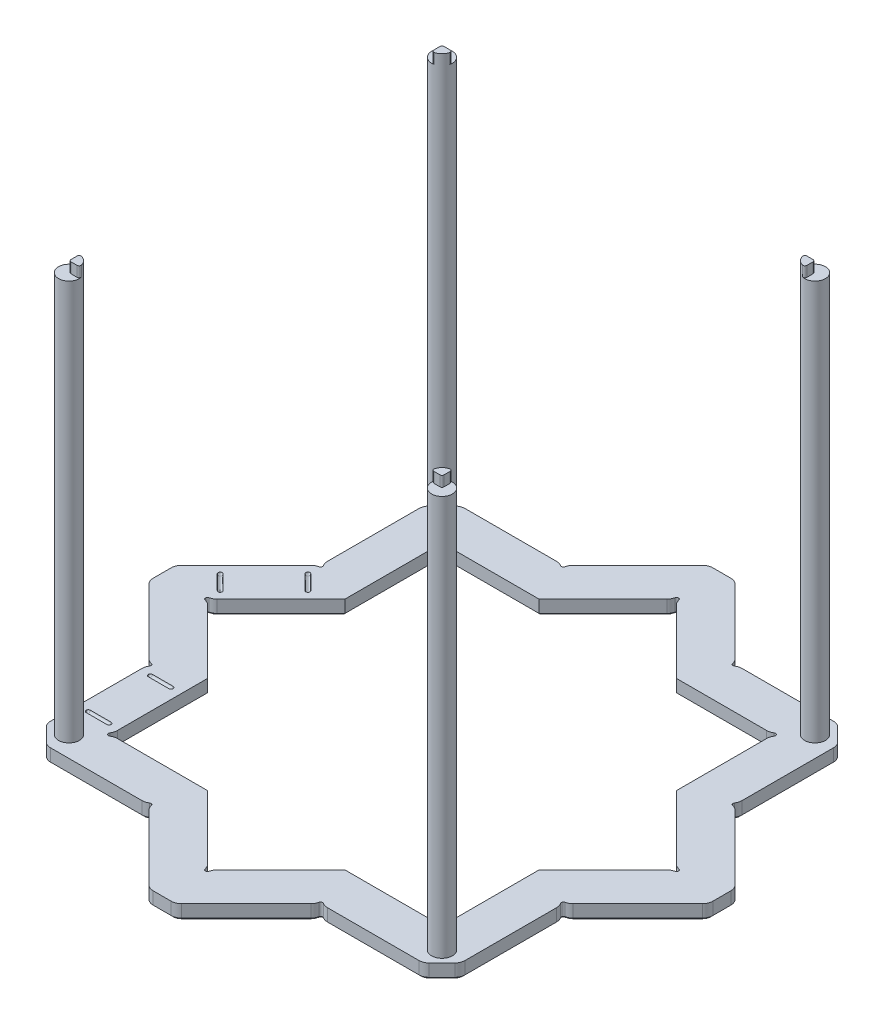
SolidWorks part; units mm, degrees
ref_plane "前视基准面" through (0, 0, 0) normal (0, 0, 1) x (1, 0, 0)
ref_plane "上视基准面" through (0, 0, 0) normal (0, 1, 0) x (1, 0, 0)
ref_plane "右视基准面" through (0, 0, 0) normal (1, 0, 0) x (0, 0, -1)
sketch "草图1" plane through (0, 0, 0) normal (0, 1, 0) x (1, 0, 0)
  line L0 (70.7107, 0) -> (0, 70.7107)
  line L1 (-50, 50) -> (50, 50)
  line L2 (-50, 50) -> (-50, -50)
  line L3 (-50, -50) -> (50, -50)
  line L4 (50, 50) -> (50, -50)
  line L5 (-50, 50) -> (50, -50) construction
  line L6 (-50, -50) -> (50, 50) construction
  line L7 (70.7107, 0) -> (0, -70.7107)
  line L8 (0, 70.7107) -> (-70.7107, 0)
  line L9 (0, -70.7107) -> (-70.7107, 0)
  line L10 (70.7107, 0) -> (-70.7107, 0) construction
  line L11 (0, 70.7107) -> (0, -70.7107) construction
  point P0 (0, 0)
  point P7 (0, 0)
  dimension "D1" = 100
  dimension "D2" = 100
  dimension "D3" = 100
  dimension "D4" = 100
extrude "凸台-拉伸1" add sketch "草图1" along normal blind 3.5 contours L0 L8 L1 | L4 L1 L0 | L7 L0 L4 | L9 L7 L3 | L4 L7 L3 | L3 L9 L2 | L9 L2 L8 | L8 L1 L2 | L9 L3 L7 L4 L0 L1 L8 L2
sketch "草图2" plane through (0, 3.5, 0) normal (0, 1, 0) x (1, 0, 0)
  line L0 (-50, -50) -> (50, 50) construction
  line L1 (-2.2703, -97.7297) -> (97.7297, 2.2703)
  line L2 (-97.7297, -2.2703) -> (2.2703, 97.7297)
  line L3 (-50, 50) -> (50, -50) construction
  line L4 (67.5, 70.7107) -> (67.5, -70.7107)
  line L5 (97.7297, 2.2703) -> (-2.2703, -97.7297)
  line L6 (70.7107, -67.5) -> (-70.7107, -67.5)
  line L7 (2.2703, -97.7297) -> (-97.7297, 2.2703)
  line L12 (-97.7297, 2.2703) -> (2.2703, -97.7297)
  line L13 (-2.2703, 97.7297) -> (97.7297, -2.2703)
  line L14 (-67.5, -70.7107) -> (-67.5, 70.7107)
  line L15 (-97.7297, -2.2703) -> (2.2703, 97.7297)
  line L16 (-70.7107, 67.5) -> (70.7107, 67.5)
  line L30 (20.7107, 50) -> (0, 70.7107)
  line L31 (0, 70.7107) -> (-20.7107, 50)
  line L32 (-20.7107, 50) -> (-50, 50)
  line L33 (-50, 50) -> (-50, 20.7107)
  line L34 (-50, 20.7107) -> (-70.7107, 0)
  line L35 (-70.7107, 0) -> (-50, -20.7107)
  line L36 (-50, -20.7107) -> (-50, -50)
  line L37 (-50, -50) -> (-20.7107, -50)
  line L38 (-20.7107, -50) -> (0, -70.7107)
  line L39 (0, -70.7107) -> (20.7107, -50)
  line L40 (20.7107, -50) -> (50, -50)
  line L41 (50, -50) -> (50, -20.7107)
  line L42 (50, -20.7107) -> (70.7107, 0)
  line L43 (70.7107, 0) -> (50, 20.7107)
  line L44 (50, 20.7107) -> (50, 50)
  line L45 (50, 50) -> (20.7107, 50)
  line L46 (20.7107, 50) -> (0, 70.7107)
  line L47 (0, 70.7107) -> (-20.7107, 50)
  line L48 (-20.7107, 50) -> (-50, 50)
  line L49 (-50, 50) -> (-50, 20.7107)
  line L50 (-50, 20.7107) -> (-70.7107, 0)
  line L51 (-70.7107, 0) -> (-50, -20.7107)
  line L52 (-50, -20.7107) -> (-50, -50)
  line L53 (-50, -50) -> (-20.7107, -50)
  line L54 (-20.7107, -50) -> (0, -70.7107)
  line L55 (0, -70.7107) -> (20.7107, -50)
  line L56 (20.7107, -50) -> (50, -50)
  line L57 (50, -50) -> (50, -20.7107)
  line L58 (50, -20.7107) -> (70.7107, 0)
  line L59 (70.7107, 0) -> (50, 20.7107)
  line L60 (50, 20.7107) -> (50, 50)
  line L61 (50, 50) -> (20.7107, 50)
  line L62 (20.7107, 50) -> (0, 70.7107)
  line L63 (50, 50) -> (20.7107, 50)
  line L64 (50, 20.7107) -> (50, 50)
  line L65 (70.7107, 0) -> (50, 20.7107)
  line L66 (50, -20.7107) -> (70.7107, 0)
  line L67 (50, -50) -> (50, -20.7107)
  line L68 (20.7107, -50) -> (50, -50)
  line L69 (0, -70.7107) -> (20.7107, -50)
  line L70 (-20.7107, -50) -> (0, -70.7107)
  line L71 (-50, -50) -> (-20.7107, -50)
  line L72 (-50, -20.7107) -> (-50, -50)
  line L73 (-70.7107, 0) -> (-50, -20.7107)
  line L74 (-50, 20.7107) -> (-70.7107, 0)
  line L75 (-50, 50) -> (-50, 20.7107)
  line L76 (-20.7107, 50) -> (-50, 50)
  line L77 (0, 70.7107) -> (-20.7107, 50)
  line L78 (20.7107, 50) -> (0, 70.7107)
  line L79 (50, 50) -> (20.7107, 50)
  line L80 (50, 20.7107) -> (50, 50)
  line L81 (70.7107, 0) -> (50, 20.7107)
  line L82 (50, -20.7107) -> (70.7107, 0)
  line L83 (50, -50) -> (50, -20.7107)
  line L84 (20.7107, -50) -> (50, -50)
  line L85 (0, -70.7107) -> (20.7107, -50)
  line L86 (-20.7107, -50) -> (0, -70.7107)
  line L87 (-50, -50) -> (-20.7107, -50)
  line L88 (-50, -20.7107) -> (-50, -50)
  line L89 (-70.7107, 0) -> (-50, -20.7107)
  line L90 (-50, 20.7107) -> (-70.7107, 0)
  line L91 (-50, 50) -> (-50, 20.7107)
  line L92 (-20.7107, 50) -> (-50, 50)
  line L93 (0, 70.7107) -> (-20.7107, 50)
  point P41 (0, 0)
  dimension "D1" = 8
  dimension "D2" = 67.5
  dimension "D3" = 67.5
  dimension "D4" = 67.5
  dimension "D5" = 67.5
  dimension "D6" = 0
  dimension "D7" = 0
extrude "切除-拉伸1" cut sketch "草图2" against normal blind 13.5
fillet "圆角1" radius 2.5 16 edges at (-50, 1.75, -45.4594) (-45.4594, 1.75, -50) (45.4594, 1.75, -50) (50, 1.75, -45.4594) (45.4594, 1.75, 50) (50, 1.75, 45.4594) (-50, 1.75, 45.4594) (-45.4594, 1.75, 50) (-3.2107, 1.75, 67.5) (3.2107, 1.75, 67.5) (67.5, 1.75, 3.2107) (67.5, 1.75, -3.2107) (3.2107, 1.75, -67.5) (-3.2107, 1.75, -67.5) (-67.5, 1.75, -3.2107) (-67.5, 1.75, 3.2107)
sketch "草图3" plane through (0, 3.5, 0) normal (0, 1, 0) x (1, 0, 0)
  line L0 (0, -56.5685) -> (56.5685, 0)
  line L1 (40, -40) -> (-40, -40)
  line L2 (40, -40) -> (40, 40)
  line L3 (40, 40) -> (-40, 40)
  line L4 (-40, -40) -> (-40, 40)
  line L5 (40, -40) -> (-40, 40) construction
  line L6 (40, 40) -> (-40, -40) construction
  line L7 (-40, -40) -> (40, -40)
  line L8 (-56.5685, 0) -> (0, -56.5685)
  line L9 (-40, 40) -> (-40, -40)
  line L10 (0, 56.5685) -> (-56.5685, 0)
  line L11 (40, 40) -> (-40, 40)
  line L12 (56.5685, 0) -> (0, 56.5685)
  point P0 (0, 0)
  point P23 (0, 0)
  dimension "D1" = 80
  dimension "D2" = 80
  dimension "D3" = 8
extrude "切除-拉伸2" cut sketch "草图3" against normal blind 13.5 contours L2 L12 L11 L10 L4 L8 L1 L0 | L0 L12 L2 | L12 L2 L3 | L11 L12 L10 | L10 L3 L9 | L4 L10 L8 | L8 L4 L7 | L1 L8 L0 | L1 L2 L0
sketch "草图5" plane through (0, 3.5, 0) normal (0, 1, 0) x (1, 0, 0)
  line L1 (-16.5685, -40) -> (-40, -40) construction
  line L3 (-16.5685, -40) -> (-40, -40)
  line L4 (40, -40) -> (16.5685, -40) construction
  line L5 (40, -40) -> (16.5685, -40)
  line L6 (40, 40) -> (16.5685, 40) construction
  line L7 (40, 40) -> (16.5685, 40)
  line L9 (-40, 16.5685) -> (-40, 40) construction
  line L10 (-40, 16.5685) -> (-40, 40)
  circle A0 centre (40, -40) radius 0.5
  circle A1 centre (40, 40) radius 0.5
  circle A2 centre (-40, 40) radius 0.5
  circle A3 centre (-40, -40) radius 0.5
  circle A4 centre (56.5685, 0) radius 0.5
  circle A5 centre (40, -40) radius 0.5
  circle A6 centre (0, -56.5685) radius 0.5
  circle A7 centre (-40, -40) radius 0.5
  circle A8 centre (-56.5685, 0) radius 0.5
  circle A9 centre (-40, 40) radius 0.5
  circle A10 centre (0, 56.5685) radius 0.5
  point P30 (0, 0)
  dimension "D1" = 1
  dimension "D2" = 1
  dimension "D3" = 1
  dimension "D4" = 1
  dimension "D5" = 8
extrude "切除-拉伸3" cut sketch "草图5" against normal blind 13.5
fillet "圆角2" radius 2.5 16 edges at (56.215, 1.75, 0.3536) (40, 1.75, -39.5) (0.3536, 1.75, -56.215) (-39.5, 1.75, -40) (-56.215, 1.75, -0.3536) (-40, 1.75, 39.5) (-0.3536, 1.75, 56.215) (39.5, 1.75, 40) (-39.5, 1.75, 40) (-40, 1.75, -39.5) (39.5, 1.75, -40) (56.215, 1.75, -0.3536) (0.3536, 1.75, 56.215) (-56.215, 1.75, 0.3536) (-0.3536, 1.75, -56.215) (40, 1.75, 39.5)
sketch "草图13" plane through (0, 3.5, 0) normal (0, 1, 0) x (1, 0, 0)
  line L1 (45, 45) -> (-45, 45) construction
  line L2 (45, 45) -> (45, -45) construction
  line L3 (45, -45) -> (-45, -45) construction
  line L4 (-45, 45) -> (-45, -45) construction
  line L5 (45, 45) -> (-45, -45) construction
  line L6 (45, -45) -> (-45, 45) construction
  line L46 (2.1751, 67.5) -> (-2.1751, 67.5)
  line L47 (20.7107, 50) -> (3.9429, 66.7678)
  line L48 (44.4239, 50) -> (20.7107, 50)
  line L49 (49.2678, 46.1916) -> (46.1916, 49.2678)
  line L50 (50, 20.7107) -> (50, 44.4239)
  line L51 (66.7678, 3.9429) -> (50, 20.7107)
  line L52 (67.5, -2.1751) -> (67.5, 2.1751)
  line L53 (50, -20.7107) -> (66.7678, -3.9429)
  line L54 (50, -44.4239) -> (50, -20.7107)
  line L55 (46.1916, -49.2678) -> (49.2678, -46.1916)
  line L56 (20.7107, -50) -> (44.4239, -50)
  line L57 (3.9429, -66.7678) -> (20.7107, -50)
  line L58 (-2.1751, -67.5) -> (2.1751, -67.5)
  line L59 (-20.7107, -50) -> (-3.9429, -66.7678)
  line L60 (-44.4239, -50) -> (-20.7107, -50)
  line L61 (-49.2678, -46.1916) -> (-46.1916, -49.2678)
  line L62 (-50, -20.7107) -> (-50, -44.4239)
  line L63 (-66.7678, -3.9429) -> (-50, -20.7107)
  line L64 (-67.5, 2.1751) -> (-67.5, -2.1751)
  line L65 (-50, 20.7107) -> (-66.7678, 3.9429)
  line L66 (-50, 44.4239) -> (-50, 20.7107)
  line L67 (-46.1916, 49.2678) -> (-49.2678, 46.1916)
  line L68 (-20.7107, 50) -> (-44.4239, 50)
  line L69 (-3.9429, 66.7678) -> (-20.7107, 50)
  line L70 (2.1751, 67.5) -> (-2.1751, 67.5)
  line L71 (20.7107, 50) -> (3.9429, 66.7678)
  line L72 (44.4239, 50) -> (20.7107, 50)
  line L73 (49.2678, 46.1916) -> (46.1916, 49.2678)
  line L74 (50, 20.7107) -> (50, 44.4239)
  line L75 (66.7678, 3.9429) -> (50, 20.7107)
  line L76 (67.5, -2.1751) -> (67.5, 2.1751)
  line L77 (50, -20.7107) -> (66.7678, -3.9429)
  line L78 (50, -44.4239) -> (50, -20.7107)
  line L79 (46.1916, -49.2678) -> (49.2678, -46.1916)
  line L80 (20.7107, -50) -> (44.4239, -50)
  line L81 (3.9429, -66.7678) -> (20.7107, -50)
  line L82 (-2.1751, -67.5) -> (2.1751, -67.5)
  line L83 (-20.7107, -50) -> (-3.9429, -66.7678)
  line L84 (-44.4239, -50) -> (-20.7107, -50)
  line L85 (-49.2678, -46.1916) -> (-46.1916, -49.2678)
  line L86 (-50, -20.7107) -> (-50, -44.4239)
  line L87 (-66.7678, -3.9429) -> (-50, -20.7107)
  line L88 (-67.5, 2.1751) -> (-67.5, -2.1751)
  line L89 (-50, 20.7107) -> (-66.7678, 3.9429)
  line L90 (-50, 44.4239) -> (-50, 20.7107)
  line L91 (-46.1916, 49.2678) -> (-49.2678, 46.1916)
  line L92 (-20.7107, 50) -> (-44.4239, 50)
  line L93 (-3.9429, 66.7678) -> (-20.7107, 50)
  circle A0 centre (45, 45) radius 2.5
  circle A1 centre (45, -45) radius 2.5
  circle A2 centre (-45, -45) radius 2.5
  circle A3 centre (-45, 45) radius 2.5
  arc A36 (3.9429, 66.7678) -> (2.1751, 67.5) centre (2.1751, 65) ccw
  arc A37 (46.1916, 49.2678) -> (44.4239, 50) centre (44.4239, 47.5) ccw
  arc A38 (50, 44.4239) -> (49.2678, 46.1916) centre (47.5, 44.4239) ccw
  arc A39 (67.5, 2.1751) -> (66.7678, 3.9429) centre (65, 2.1751) ccw
  arc A40 (66.7678, -3.9429) -> (67.5, -2.1751) centre (65, -2.1751) ccw
  arc A41 (49.2678, -46.1916) -> (50, -44.4239) centre (47.5, -44.4239) ccw
  arc A42 (44.4239, -50) -> (46.1916, -49.2678) centre (44.4239, -47.5) ccw
  arc A43 (2.1751, -67.5) -> (3.9429, -66.7678) centre (2.1751, -65) ccw
  arc A44 (-3.9429, -66.7678) -> (-2.1751, -67.5) centre (-2.1751, -65) ccw
  arc A45 (-46.1916, -49.2678) -> (-44.4239, -50) centre (-44.4239, -47.5) ccw
  arc A46 (-50, -44.4239) -> (-49.2678, -46.1916) centre (-47.5, -44.4239) ccw
  arc A47 (-67.5, -2.1751) -> (-66.7678, -3.9429) centre (-65, -2.1751) ccw
  arc A48 (-66.7678, 3.9429) -> (-67.5, 2.1751) centre (-65, 2.1751) ccw
  arc A49 (-49.2678, 46.1916) -> (-50, 44.4239) centre (-47.5, 44.4239) ccw
  arc A50 (-44.4239, 50) -> (-46.1916, 49.2678) centre (-44.4239, 47.5) ccw
  arc A51 (-2.1751, 67.5) -> (-3.9429, 66.7678) centre (-2.1751, 65) ccw
  arc A52 (3.9429, 66.7678) -> (2.1751, 67.5) centre (2.1751, 65) ccw
  arc A53 (46.1916, 49.2678) -> (44.4239, 50) centre (44.4239, 47.5) ccw
  arc A54 (50, 44.4239) -> (49.2678, 46.1916) centre (47.5, 44.4239) ccw
  arc A55 (67.5, 2.1751) -> (66.7678, 3.9429) centre (65, 2.1751) ccw
  arc A56 (66.7678, -3.9429) -> (67.5, -2.1751) centre (65, -2.1751) ccw
  arc A57 (49.2678, -46.1916) -> (50, -44.4239) centre (47.5, -44.4239) ccw
  arc A58 (44.4239, -50) -> (46.1916, -49.2678) centre (44.4239, -47.5) ccw
  arc A59 (2.1751, -67.5) -> (3.9429, -66.7678) centre (2.1751, -65) ccw
  arc A60 (-3.9429, -66.7678) -> (-2.1751, -67.5) centre (-2.1751, -65) ccw
  arc A61 (-46.1916, -49.2678) -> (-44.4239, -50) centre (-44.4239, -47.5) ccw
  arc A62 (-50, -44.4239) -> (-49.2678, -46.1916) centre (-47.5, -44.4239) ccw
  arc A63 (-67.5, -2.1751) -> (-66.7678, -3.9429) centre (-65, -2.1751) ccw
  arc A64 (-66.7678, 3.9429) -> (-67.5, 2.1751) centre (-65, 2.1751) ccw
  arc A65 (-49.2678, 46.1916) -> (-50, 44.4239) centre (-47.5, 44.4239) ccw
  arc A66 (-44.4239, 50) -> (-46.1916, 49.2678) centre (-44.4239, 47.5) ccw
  arc A67 (-2.1751, 67.5) -> (-3.9429, 66.7678) centre (-2.1751, 65) ccw
  point P2 (0, 0)
  dimension "D4" = 5
  dimension "D5" = 5
  dimension "D6" = 5
  dimension "D7" = 5
  dimension "D2" = 90
  dimension "D3" = 90
  dimension "D8" = 0
extrude "凸台-拉伸5" add sketch "草图13" along normal blind 96.5 contours A2 | A1 | A0 | A3
sketch "草图14" plane through (0, 100, 0) normal (0, 1, 0) x (1, 0, 0)
  line L1 (45, 45) -> (-45, 45)
  line L2 (45, 45) -> (45, -45)
  line L3 (45, -45) -> (-45, -45)
  line L4 (-45, 45) -> (-45, -45)
  circle A1 centre (-45, -45) radius 2.5
  circle A2 centre (-45, -45) radius 2.5
  circle A3 centre (45, -45) radius 2.5
  circle A4 centre (45, -45) radius 2.5
  circle A5 centre (45, 45) radius 2.5
  circle A6 centre (45, 45) radius 2.5
  circle A7 centre (-45, 45) radius 2.5
  circle A8 centre (-45, 45) radius 2.5
  circle M5 centre (-45, -45) radius 2.5
  dimension "D1" = 0
  dimension "D2" = 0
  dimension "D3" = 0
  dimension "D4" = 0
extrude "凸台-拉伸6" add sketch "草图14" along normal blind 2.5 contours L2 A4 L3 | L4 L3 M5 | L4 A8 L1 | L1 A6 L2
fillet "圆角7" radius 0.5 12 edges at (45, 101.25, 42.5) (42.5, 101.25, 45) (45, 101.25, 45) (-42.5, 101.25, 45) (-45, 101.25, 45) (-45, 101.25, 42.5) (-45, 101.25, -42.5) (-45, 101.25, -45) (-42.5, 101.25, -45) (45, 101.25, -42.5) (42.5, 101.25, -45) (45, 101.25, -45)
sketch "草图15" plane through (0, 0, 0) normal (0, -1, 0) x (1, 0, 0)
  line L0 (-44.5, -44.5) -> (-44.5, 44.5)
  line L1 (-45, -45) -> (45, -45)
  line L2 (-45, -45) -> (-45, 45)
  line L3 (-45, 45) -> (45, 45)
  line L4 (45, -45) -> (45, 45)
  line L5 (-44.5, 44.5) -> (44.5, 44.5)
  line L6 (44.5, -44.5) -> (44.5, 44.5)
  line L7 (-44.5, -44.5) -> (44.5, -44.5)
  line L8 (46.1916, -49.2678) -> (49.2678, -46.1916)
  line L9 (46.1916, -49.2678) -> (49.2678, -46.1916)
  line L10 (50, -44.4239) -> (50, -20.7107)
  line L11 (50, -44.4239) -> (50, -20.7107)
  line L12 (50, -20.7107) -> (66.7678, -3.9429)
  line L13 (50, -20.7107) -> (66.7678, -3.9429)
  line L14 (67.5, -2.1751) -> (67.5, 2.1751)
  line L15 (67.5, -2.1751) -> (67.5, 2.1751)
  line L48 (66.7678, 3.9429) -> (50, 20.7107)
  line L49 (66.7678, 3.9429) -> (50, 20.7107)
  line L50 (50, 20.7107) -> (50, 44.4239)
  line L51 (50, 20.7107) -> (50, 44.4239)
  line L52 (49.2678, 46.1916) -> (46.1916, 49.2678)
  line L53 (49.2678, 46.1916) -> (46.1916, 49.2678)
  line L54 (44.4239, 50) -> (20.7107, 50)
  line L55 (44.4239, 50) -> (20.7107, 50)
  line L56 (20.7107, 50) -> (3.9429, 66.7678)
  line L57 (20.7107, 50) -> (3.9429, 66.7678)
  line L58 (2.1751, 67.5) -> (-2.1751, 67.5)
  line L59 (2.1751, 67.5) -> (-2.1751, 67.5)
  line L60 (-3.9429, 66.7678) -> (-20.7107, 50)
  line L61 (-3.9429, 66.7678) -> (-20.7107, 50)
  line L62 (-20.7107, 50) -> (-44.4239, 50)
  line L63 (-20.7107, 50) -> (-44.4239, 50)
  line L64 (-46.1916, 49.2678) -> (-49.2678, 46.1916)
  line L65 (-46.1916, 49.2678) -> (-49.2678, 46.1916)
  line L66 (-50, 44.4239) -> (-50, 20.7107)
  line L67 (-50, 44.4239) -> (-50, 20.7107)
  line L68 (-50, 20.7107) -> (-66.7678, 3.9429)
  line L69 (-50, 20.7107) -> (-66.7678, 3.9429)
  line L70 (-67.5, 2.1751) -> (-67.5, -2.1751)
  line L71 (-67.5, 2.1751) -> (-67.5, -2.1751)
  line L72 (-66.7678, -3.9429) -> (-50, -20.7107)
  line L73 (-66.7678, -3.9429) -> (-50, -20.7107)
  line L74 (-50, -20.7107) -> (-50, -44.4239)
  line L75 (-50, -20.7107) -> (-50, -44.4239)
  line L76 (-49.2678, -46.1916) -> (-46.1916, -49.2678)
  line L77 (-49.2678, -46.1916) -> (-46.1916, -49.2678)
  line L78 (-44.4239, -50) -> (-20.7107, -50)
  line L79 (-44.4239, -50) -> (-20.7107, -50)
  line L80 (-20.7107, -50) -> (-3.9429, -66.7678)
  line L81 (-20.7107, -50) -> (-3.9429, -66.7678)
  line L82 (-2.1751, -67.5) -> (2.1751, -67.5)
  line L83 (-2.1751, -67.5) -> (2.1751, -67.5)
  line L84 (3.9429, -66.7678) -> (20.7107, -50)
  line L85 (3.9429, -66.7678) -> (20.7107, -50)
  line L86 (20.7107, -50) -> (44.4239, -50)
  line L87 (20.7107, -50) -> (44.4239, -50)
  circle A1 centre (45, -45) radius 2.5
  circle A2 centre (45, -45) radius 2.5
  circle A3 centre (-45, 45) radius 2.5
  circle A4 centre (-45, 45) radius 2.5
  circle A5 centre (45, 45) radius 2.5
  circle A6 centre (45, 45) radius 2.5
  circle A7 centre (-45, -45) radius 2.5
  circle A8 centre (-45, -45) radius 2.5
  arc A14 (49.2678, -46.1916) -> (50, -44.4239) centre (47.5, -44.4239) ccw
  arc A15 (49.2678, -46.1916) -> (50, -44.4239) centre (47.5, -44.4239) ccw
  arc A16 (66.7678, -3.9429) -> (67.5, -2.1751) centre (65, -2.1751) ccw
  arc A17 (44.4239, -50) -> (46.1916, -49.2678) centre (44.4239, -47.5) ccw
  arc A18 (66.7678, -3.9429) -> (67.5, -2.1751) centre (65, -2.1751) ccw
  arc A19 (67.5, 2.1751) -> (66.7678, 3.9429) centre (65, 2.1751) ccw
  arc A20 (67.5, 2.1751) -> (66.7678, 3.9429) centre (65, 2.1751) ccw
  arc A21 (50, 44.4239) -> (49.2678, 46.1916) centre (47.5, 44.4239) ccw
  arc A25 (44.4239, -50) -> (46.1916, -49.2678) centre (44.4239, -47.5) ccw
  arc A40 (50, 44.4239) -> (49.2678, 46.1916) centre (47.5, 44.4239) ccw
  arc A41 (46.1916, 49.2678) -> (44.4239, 50) centre (44.4239, 47.5) ccw
  arc A42 (46.1916, 49.2678) -> (44.4239, 50) centre (44.4239, 47.5) ccw
  arc A43 (3.9429, 66.7678) -> (2.1751, 67.5) centre (2.1751, 65) ccw
  arc A44 (3.9429, 66.7678) -> (2.1751, 67.5) centre (2.1751, 65) ccw
  arc A45 (-2.1751, 67.5) -> (-3.9429, 66.7678) centre (-2.1751, 65) ccw
  arc A46 (-2.1751, 67.5) -> (-3.9429, 66.7678) centre (-2.1751, 65) ccw
  arc A47 (-44.4239, 50) -> (-46.1916, 49.2678) centre (-44.4239, 47.5) ccw
  arc A48 (-44.4239, 50) -> (-46.1916, 49.2678) centre (-44.4239, 47.5) ccw
  arc A49 (-49.2678, 46.1916) -> (-50, 44.4239) centre (-47.5, 44.4239) ccw
  arc A50 (-49.2678, 46.1916) -> (-50, 44.4239) centre (-47.5, 44.4239) ccw
  arc A51 (-66.7678, 3.9429) -> (-67.5, 2.1751) centre (-65, 2.1751) ccw
  arc A52 (-66.7678, 3.9429) -> (-67.5, 2.1751) centre (-65, 2.1751) ccw
  arc A53 (-67.5, -2.1751) -> (-66.7678, -3.9429) centre (-65, -2.1751) ccw
  arc A54 (-67.5, -2.1751) -> (-66.7678, -3.9429) centre (-65, -2.1751) ccw
  arc A55 (-50, -44.4239) -> (-49.2678, -46.1916) centre (-47.5, -44.4239) ccw
  arc A56 (-50, -44.4239) -> (-49.2678, -46.1916) centre (-47.5, -44.4239) ccw
  arc A57 (-46.1916, -49.2678) -> (-44.4239, -50) centre (-44.4239, -47.5) ccw
  arc A58 (-46.1916, -49.2678) -> (-44.4239, -50) centre (-44.4239, -47.5) ccw
  arc A59 (-3.9429, -66.7678) -> (-2.1751, -67.5) centre (-2.1751, -65) ccw
  arc A60 (-3.9429, -66.7678) -> (-2.1751, -67.5) centre (-2.1751, -65) ccw
  arc A61 (2.1751, -67.5) -> (3.9429, -66.7678) centre (2.1751, -65) ccw
  arc A62 (2.1751, -67.5) -> (3.9429, -66.7678) centre (2.1751, -65) ccw
  dimension "D1" = 0
  dimension "D2" = 0
  dimension "D3" = 0
  dimension "D4" = 0
  dimension "D5" = 0
  dimension "D6" = 0.5
extrude "切除-拉伸8" cut sketch "草图15" against normal blind 0.5 contours L3 A6 L5 L6 L4 | L4 A2 L6 L7 L1 | L1 A8 L7 L0 L2 | L2 A4 L0 L5 L3
sketch "草图18" plane through (0, 3.5, 0) normal (0, 1, 0) x (1, 0, 0)
  line L24 (20.7107, 50) -> (3.9429, 66.7678)
  line L25 (2.1751, 67.5) -> (-2.1751, 67.5)
  line L26 (-3.9429, 66.7678) -> (-20.7107, 50)
  line L27 (-20.7107, 50) -> (-44.4239, 50)
  line L28 (-46.1916, 49.2678) -> (-49.2678, 46.1916)
  line L29 (-50, 44.4239) -> (-50, 20.7107)
  line L30 (-50, 20.7107) -> (-66.7678, 3.9429)
  line L31 (-67.5, 2.1751) -> (-67.5, -2.1751)
  line L32 (-66.7678, -3.9429) -> (-50, -20.7107)
  line L33 (-50, -20.7107) -> (-50, -44.4239)
  line L34 (-49.2678, -46.1916) -> (-46.1916, -49.2678)
  line L35 (-44.4239, -50) -> (-20.7107, -50)
  line L36 (-20.7107, -50) -> (-3.9429, -66.7678)
  line L37 (-2.1751, -67.5) -> (2.1751, -67.5)
  line L38 (3.9429, -66.7678) -> (20.7107, -50)
  line L39 (20.7107, -50) -> (44.4239, -50)
  line L40 (46.1916, -49.2678) -> (49.2678, -46.1916)
  line L41 (50, -44.4239) -> (50, -20.7107)
  line L42 (50, -20.7107) -> (66.7678, -3.9429)
  line L43 (67.5, -2.1751) -> (67.5, 2.1751)
  line L44 (66.7678, 3.9429) -> (50, 20.7107)
  line L45 (50, 20.7107) -> (50, 44.4239)
  line L46 (49.2678, 46.1916) -> (46.1916, 49.2678)
  line L47 (44.4239, 50) -> (20.7107, 50)
  line L48 (20.7107, 50) -> (3.9429, 66.7678)
  line L49 (2.1751, 67.5) -> (-2.1751, 67.5)
  line L50 (-3.9429, 66.7678) -> (-20.7107, 50)
  line L51 (-20.7107, 50) -> (-44.4239, 50)
  line L52 (-46.1916, 49.2678) -> (-49.2678, 46.1916)
  line L53 (-50, 44.4239) -> (-50, 20.7107)
  line L54 (-50, 20.7107) -> (-66.7678, 3.9429)
  line L55 (-67.5, 2.1751) -> (-67.5, -2.1751)
  line L56 (-66.7678, -3.9429) -> (-50, -20.7107)
  line L57 (-50, -20.7107) -> (-50, -44.4239)
  line L58 (-49.2678, -46.1916) -> (-46.1916, -49.2678)
  line L59 (-44.4239, -50) -> (-20.7107, -50)
  line L60 (-20.7107, -50) -> (-3.9429, -66.7678)
  line L61 (-2.1751, -67.5) -> (2.1751, -67.5)
  line L62 (3.9429, -66.7678) -> (20.7107, -50)
  line L63 (20.7107, -50) -> (44.4239, -50)
  line L64 (46.1916, -49.2678) -> (49.2678, -46.1916)
  line L65 (50, -44.4239) -> (50, -20.7107)
  line L66 (50, -20.7107) -> (66.7678, -3.9429)
  line L67 (67.5, -2.1751) -> (67.5, 2.1751)
  line L68 (66.7678, 3.9429) -> (50, 20.7107)
  line L69 (50, 20.7107) -> (50, 44.4239)
  line L70 (49.2678, 46.1916) -> (46.1916, 49.2678)
  line L71 (44.4239, 50) -> (20.7107, 50)
  circle A0 centre (50, 20.7107) radius 0.5
  circle A1 centre (50, -20.7107) radius 0.5
  circle A2 centre (20.7107, -50) radius 0.5
  circle A3 centre (-20.7107, -50) radius 0.5
  circle A4 centre (-50, -20.7107) radius 0.5
  circle A5 centre (-50, 20.7107) radius 0.5
  circle A6 centre (-20.7107, 50) radius 0.5
  circle A7 centre (20.7107, 50) radius 0.5
  arc A16 (3.9429, 66.7678) -> (2.1751, 67.5) centre (2.1751, 65) ccw
  arc A17 (-2.1751, 67.5) -> (-3.9429, 66.7678) centre (-2.1751, 65) ccw
  arc A18 (-44.4239, 50) -> (-46.1916, 49.2678) centre (-44.4239, 47.5) ccw
  arc A19 (-49.2678, 46.1916) -> (-50, 44.4239) centre (-47.5, 44.4239) ccw
  arc A20 (-66.7678, 3.9429) -> (-67.5, 2.1751) centre (-65, 2.1751) ccw
  arc A21 (-67.5, -2.1751) -> (-66.7678, -3.9429) centre (-65, -2.1751) ccw
  arc A22 (-50, -44.4239) -> (-49.2678, -46.1916) centre (-47.5, -44.4239) ccw
  arc A23 (-46.1916, -49.2678) -> (-44.4239, -50) centre (-44.4239, -47.5) ccw
  arc A24 (-3.9429, -66.7678) -> (-2.1751, -67.5) centre (-2.1751, -65) ccw
  arc A25 (2.1751, -67.5) -> (3.9429, -66.7678) centre (2.1751, -65) ccw
  arc A26 (44.4239, -50) -> (46.1916, -49.2678) centre (44.4239, -47.5) ccw
  arc A27 (49.2678, -46.1916) -> (50, -44.4239) centre (47.5, -44.4239) ccw
  arc A28 (66.7678, -3.9429) -> (67.5, -2.1751) centre (65, -2.1751) ccw
  arc A29 (67.5, 2.1751) -> (66.7678, 3.9429) centre (65, 2.1751) ccw
  arc A30 (50, 44.4239) -> (49.2678, 46.1916) centre (47.5, 44.4239) ccw
  arc A31 (46.1916, 49.2678) -> (44.4239, 50) centre (44.4239, 47.5) ccw
  arc A32 (3.9429, 66.7678) -> (2.1751, 67.5) centre (2.1751, 65) ccw
  arc A33 (-2.1751, 67.5) -> (-3.9429, 66.7678) centre (-2.1751, 65) ccw
  arc A34 (-44.4239, 50) -> (-46.1916, 49.2678) centre (-44.4239, 47.5) ccw
  arc A35 (-49.2678, 46.1916) -> (-50, 44.4239) centre (-47.5, 44.4239) ccw
  arc A36 (-66.7678, 3.9429) -> (-67.5, 2.1751) centre (-65, 2.1751) ccw
  arc A37 (-67.5, -2.1751) -> (-66.7678, -3.9429) centre (-65, -2.1751) ccw
  arc A38 (-50, -44.4239) -> (-49.2678, -46.1916) centre (-47.5, -44.4239) ccw
  arc A39 (-46.1916, -49.2678) -> (-44.4239, -50) centre (-44.4239, -47.5) ccw
  arc A40 (-3.9429, -66.7678) -> (-2.1751, -67.5) centre (-2.1751, -65) ccw
  arc A41 (2.1751, -67.5) -> (3.9429, -66.7678) centre (2.1751, -65) ccw
  arc A42 (44.4239, -50) -> (46.1916, -49.2678) centre (44.4239, -47.5) ccw
  arc A43 (49.2678, -46.1916) -> (50, -44.4239) centre (47.5, -44.4239) ccw
  arc A44 (66.7678, -3.9429) -> (67.5, -2.1751) centre (65, -2.1751) ccw
  arc A45 (67.5, 2.1751) -> (66.7678, 3.9429) centre (65, 2.1751) ccw
  arc A46 (50, 44.4239) -> (49.2678, 46.1916) centre (47.5, 44.4239) ccw
  arc A47 (46.1916, 49.2678) -> (44.4239, 50) centre (44.4239, 47.5) ccw
  point P74 (0, 0)
  dimension "D2" = 1
  dimension "D1" = 0
  dimension "D3" = 8
extrude "切除-拉伸9" cut sketch "草图18" against normal blind 10 contours L69 A0 L68 | L66 A1 L65 | L63 A2 L62 | L60 A3 L59 | L57 A4 L56 | L54 A5 L53 | L51 A6 L50 | L48 A7 L71
fillet "圆角8" radius 2.5 16 edges at (50.3536, 1.75, -20.3571) (50, 1.75, -21.2107) (21.2107, 1.75, -50) (20.3571, 1.75, -50.3536) (-20.3571, 1.75, -50.3536) (-21.2107, 1.75, -50) (-50.3536, 1.75, -20.3571) (-50, 1.75, -21.2107) (-50.3536, 1.75, 20.3571) (-50, 1.75, 21.2107) (-21.2107, 1.75, 50) (-20.3571, 1.75, 50.3536) (20.3571, 1.75, 50.3536) (21.2107, 1.75, 50) (50, 1.75, 21.2107) (50.3536, 1.75, 20.3571)
chamfer "倒角1" distance 0.5 angle 45 104 edges at (49.8936, 0, -21.6473) (50, 0, -33.3964) (49.8097, 0, -45.3806) (47.7297, 0, -47.7297) (45.3806, 0, -49.8097) (33.3964, 0, -50) (21.6473, 0, -49.8936) (20.5193, 0, -49.5381) (19.9731, 0, -50.587) (11.7405, 0, -58.9702) (3.1319, 0, -67.3097) (0, 0, -67.5) (-3.1319, 0, -67.3097) (-11.7405, 0, -58.9702) (-19.9731, 0, -50.587) (-20.5193, 0, -49.5381) (-21.6473, 0, -49.8936) (-33.3964, 0, -50) (-45.3806, 0, -49.8097) (-47.7297, 0, -47.7297) (-49.8097, 0, -45.3806) (-50, 0, -33.3964) (-49.8936, 0, -21.6473) (-49.5381, 0, -20.5193) (-50.587, 0, -19.9731) (-58.9702, 0, -11.7405) (-67.3097, 0, -3.1319) (-67.5, 0, 0) (-67.3097, 0, 3.1319) (-58.9702, 0, 11.7405) (-50.587, 0, 19.9731) (-49.5381, 0, 20.5193) (-49.8936, 0, 21.6473) (-50, 0, 33.3964) (-49.8097, 0, 45.3806) (-47.7297, 0, 47.7297) (-45.3806, 0, 49.8097) (-33.3964, 0, 50) (-21.6473, 0, 49.8936) (-20.5193, 0, 49.5381) (-19.9731, 0, 50.587) (-11.7405, 0, 58.9702) (-3.1319, 0, 67.3097) (0, 0, 67.5) (3.1319, 0, 67.3097) (11.7405, 0, 58.9702) (19.9731, 0, 50.587) (20.5193, 0, 49.5381) (21.6473, 0, 49.8936) (33.3964, 0, 50) (45.3806, 0, 49.8097) (47.7297, 0, 47.7297) (49.8097, 0, 45.3806) (50, 0, 33.3964) (49.8936, 0, 21.6473) (49.5381, 0, 20.5193) (50.587, 0, 19.9731) (58.9702, 0, 11.7405) (67.3097, 0, 3.1319) (67.5, 0, 0) (67.3097, 0, -3.1319) (58.9702, 0, -11.7405) (50.587, 0, -19.9731) (49.5381, 0, -20.5193) (-40, 0, -27.4551) (-40.1064, 0, -39.0634) (-40.3536, 0, -40.3536) (-39.0634, 0, -40.1064) (-27.4551, 0, -40) (-8.8706, 0, -47.698) (-0.7376, 0, -55.9815) (0, 0, -57.0685) (0.7376, 0, -55.9815) (8.8706, 0, -47.698) (27.4551, 0, -40) (39.0634, 0, -40.1064) (40.3536, 0, -40.3536) (40.1064, 0, -39.0634) (40, 0, -27.4551) (47.698, 0, -8.8706) (55.9815, 0, -0.7376) (57.0685, 0, 0) (55.9815, 0, 0.7376) (47.698, 0, 8.8706) (40, 0, 27.4551) (40.1064, 0, 39.0634) (40.3536, 0, 40.3536) (39.0634, 0, 40.1064) (27.4551, 0, 40) (8.8706, 0, 47.698) (0.7376, 0, 55.9815) (0, 0, 57.0685) (-0.7376, 0, 55.9815) (-8.8706, 0, 47.698) (-27.4551, 0, 40) (-39.0634, 0, 40.1064) (-40.3536, 0, 40.3536) (-40.1064, 0, 39.0634) (-40, 0, 27.4551) (-47.698, 0, 8.8706) (-55.9815, 0, 0.7376) (-57.0685, 0, 0) (-55.9815, 0, -0.7376) (-47.698, 0, -8.8706)
sketch "草图19" plane through (0, 3.5, 0) normal (0, 1, 0) x (1, 0, 0)
  line L0 (-48, -22.369) -> (-48, -44.4239)
  line L3 (-42, -22.369) -> (-42, -44.4239)
  line L5 (-48, -38.3417) -> (-42, -38.3417)
  line L6 (-48, -38.3417) -> (-48, -37.3417)
  line L7 (-48, -37.3417) -> (-42, -37.3417)
  line L8 (-42, -38.3417) -> (-42, -37.3417)
  line L9 (-48, -23.369) -> (-42, -23.369)
  line L10 (-48, -23.369) -> (-48, -22.369)
  line L11 (-48, -22.369) -> (-42, -22.369)
  line L12 (-42, -23.369) -> (-42, -22.369)
  line L24 (66.7678, 3.9429) -> (51.1726, 19.5381)
  line L25 (50, 22.369) -> (50, 44.4239)
  line L26 (49.2678, 46.1916) -> (46.1916, 49.2678)
  line L27 (44.4239, 50) -> (22.369, 50)
  line L28 (19.5381, 51.1726) -> (3.9429, 66.7678)
  line L29 (2.1751, 67.5) -> (-2.1751, 67.5)
  line L30 (-3.9429, 66.7678) -> (-19.5381, 51.1726)
  line L31 (-22.369, 50) -> (-44.4239, 50)
  line L32 (-46.1916, 49.2678) -> (-49.2678, 46.1916)
  line L33 (-50, 44.4239) -> (-50, 22.369)
  line L34 (-51.1726, 19.5381) -> (-66.7678, 3.9429)
  line L35 (-67.5, 2.1751) -> (-67.5, -2.1751)
  line L36 (-66.7678, -3.9429) -> (-51.1726, -19.5381)
  line L37 (-50, -22.369) -> (-50, -44.4239)
  line L38 (-49.2678, -46.1916) -> (-46.1916, -49.2678)
  line L39 (-44.4239, -50) -> (-22.369, -50)
  line L40 (-19.5381, -51.1726) -> (-3.9429, -66.7678)
  line L41 (-2.1751, -67.5) -> (2.1751, -67.5)
  line L42 (3.9429, -66.7678) -> (19.5381, -51.1726)
  line L43 (22.369, -50) -> (44.4239, -50)
  line L44 (46.1916, -49.2678) -> (49.2678, -46.1916)
  line L45 (50, -44.4239) -> (50, -22.369)
  line L46 (51.1726, -19.5381) -> (66.7678, -3.9429)
  line L47 (67.5, -2.1751) -> (67.5, 2.1751)
  line L48 (66.7678, 3.9429) -> (51.1726, 19.5381)
  line L49 (50, 22.369) -> (50, 44.4239)
  line L50 (49.2678, 46.1916) -> (46.1916, 49.2678)
  line L51 (44.4239, 50) -> (22.369, 50)
  line L52 (19.5381, 51.1726) -> (3.9429, 66.7678)
  line L53 (2.1751, 67.5) -> (-2.1751, 67.5)
  line L54 (-3.9429, 66.7678) -> (-19.5381, 51.1726)
  line L55 (-22.369, 50) -> (-44.4239, 50)
  line L56 (-46.1916, 49.2678) -> (-49.2678, 46.1916)
  line L57 (-50, 44.4239) -> (-50, 22.369)
  line L58 (-51.1726, 19.5381) -> (-66.7678, 3.9429)
  line L59 (-67.5, 2.1751) -> (-67.5, -2.1751)
  line L60 (-66.7678, -3.9429) -> (-51.1726, -19.5381)
  line L61 (-50, -22.369) -> (-50, -44.4239)
  line L62 (-49.2678, -46.1916) -> (-46.1916, -49.2678)
  line L63 (-44.4239, -50) -> (-22.369, -50)
  line L64 (-19.5381, -51.1726) -> (-3.9429, -66.7678)
  line L65 (-2.1751, -67.5) -> (2.1751, -67.5)
  line L66 (3.9429, -66.7678) -> (19.5381, -51.1726)
  line L67 (22.369, -50) -> (44.4239, -50)
  line L68 (46.1916, -49.2678) -> (49.2678, -46.1916)
  line L69 (50, -44.4239) -> (50, -22.369)
  line L70 (51.1726, -19.5381) -> (66.7678, -3.9429)
  line L71 (67.5, -2.1751) -> (67.5, 2.1751)
  arc A40 (51.1726, 19.5381) -> (49.9008, 20.2206) centre (49.4048, 17.7703) ccw
  arc A41 (49.5833, 20.9871) -> (49.9008, 20.2206) centre (50, 20.7107) ccw
  arc A42 (49.5833, 20.9871) -> (50, 22.369) centre (47.5, 22.369) ccw
  arc A43 (50, 44.4239) -> (49.2678, 46.1916) centre (47.5, 44.4239) ccw
  arc A44 (46.1916, 49.2678) -> (44.4239, 50) centre (44.4239, 47.5) ccw
  arc A45 (22.369, 50) -> (20.9871, 49.5833) centre (22.369, 47.5) ccw
  arc A46 (20.2206, 49.9008) -> (20.9871, 49.5833) centre (20.7107, 50) ccw
  arc A47 (20.2206, 49.9008) -> (19.5381, 51.1726) centre (17.7703, 49.4048) ccw
  arc A48 (3.9429, 66.7678) -> (2.1751, 67.5) centre (2.1751, 65) ccw
  arc A49 (-2.1751, 67.5) -> (-3.9429, 66.7678) centre (-2.1751, 65) ccw
  arc A50 (-19.5381, 51.1726) -> (-20.2206, 49.9008) centre (-17.7703, 49.4048) ccw
  arc A51 (-20.9871, 49.5833) -> (-20.2206, 49.9008) centre (-20.7107, 50) ccw
  arc A52 (-20.9871, 49.5833) -> (-22.369, 50) centre (-22.369, 47.5) ccw
  arc A53 (-44.4239, 50) -> (-46.1916, 49.2678) centre (-44.4239, 47.5) ccw
  arc A54 (-49.2678, 46.1916) -> (-50, 44.4239) centre (-47.5, 44.4239) ccw
  arc A55 (-50, 22.369) -> (-49.5833, 20.9871) centre (-47.5, 22.369) ccw
  arc A56 (-49.9008, 20.2206) -> (-49.5833, 20.9871) centre (-50, 20.7107) ccw
  arc A57 (-49.9008, 20.2206) -> (-51.1726, 19.5381) centre (-49.4048, 17.7703) ccw
  arc A58 (-66.7678, 3.9429) -> (-67.5, 2.1751) centre (-65, 2.1751) ccw
  arc A59 (-67.5, -2.1751) -> (-66.7678, -3.9429) centre (-65, -2.1751) ccw
  arc A60 (-51.1726, -19.5381) -> (-49.9008, -20.2206) centre (-49.4048, -17.7703) ccw
  arc A61 (-49.5833, -20.9871) -> (-49.9008, -20.2206) centre (-50, -20.7107) ccw
  arc A62 (-49.5833, -20.9871) -> (-50, -22.369) centre (-47.5, -22.369) ccw
  arc A63 (-50, -44.4239) -> (-49.2678, -46.1916) centre (-47.5, -44.4239) ccw
  arc A64 (-46.1916, -49.2678) -> (-44.4239, -50) centre (-44.4239, -47.5) ccw
  arc A65 (-22.369, -50) -> (-20.9871, -49.5833) centre (-22.369, -47.5) ccw
  arc A66 (-20.2206, -49.9008) -> (-20.9871, -49.5833) centre (-20.7107, -50) ccw
  arc A67 (-20.2206, -49.9008) -> (-19.5381, -51.1726) centre (-17.7703, -49.4048) ccw
  arc A68 (-3.9429, -66.7678) -> (-2.1751, -67.5) centre (-2.1751, -65) ccw
  arc A69 (2.1751, -67.5) -> (3.9429, -66.7678) centre (2.1751, -65) ccw
  arc A70 (19.5381, -51.1726) -> (20.2206, -49.9008) centre (17.7703, -49.4048) ccw
  arc A71 (20.9871, -49.5833) -> (20.2206, -49.9008) centre (20.7107, -50) ccw
  arc A72 (20.9871, -49.5833) -> (22.369, -50) centre (22.369, -47.5) ccw
  arc A73 (44.4239, -50) -> (46.1916, -49.2678) centre (44.4239, -47.5) ccw
  arc A74 (49.2678, -46.1916) -> (50, -44.4239) centre (47.5, -44.4239) ccw
  arc A75 (50, -22.369) -> (49.5833, -20.9871) centre (47.5, -22.369) ccw
  arc A76 (49.9008, -20.2206) -> (49.5833, -20.9871) centre (50, -20.7107) ccw
  arc A77 (49.9008, -20.2206) -> (51.1726, -19.5381) centre (49.4048, -17.7703) ccw
  arc A78 (66.7678, -3.9429) -> (67.5, -2.1751) centre (65, -2.1751) ccw
  arc A79 (67.5, 2.1751) -> (66.7678, 3.9429) centre (65, 2.1751) ccw
  arc A80 (51.1726, 19.5381) -> (49.9008, 20.2206) centre (49.4048, 17.7703) ccw
  arc A81 (49.5833, 20.9871) -> (49.9008, 20.2206) centre (50, 20.7107) ccw
  arc A82 (49.5833, 20.9871) -> (50, 22.369) centre (47.5, 22.369) ccw
  arc A83 (50, 44.4239) -> (49.2678, 46.1916) centre (47.5, 44.4239) ccw
  arc A84 (46.1916, 49.2678) -> (44.4239, 50) centre (44.4239, 47.5) ccw
  arc A85 (22.369, 50) -> (20.9871, 49.5833) centre (22.369, 47.5) ccw
  arc A86 (20.2206, 49.9008) -> (20.9871, 49.5833) centre (20.7107, 50) ccw
  arc A87 (20.2206, 49.9008) -> (19.5381, 51.1726) centre (17.7703, 49.4048) ccw
  arc A88 (3.9429, 66.7678) -> (2.1751, 67.5) centre (2.1751, 65) ccw
  arc A89 (-2.1751, 67.5) -> (-3.9429, 66.7678) centre (-2.1751, 65) ccw
  arc A90 (-19.5381, 51.1726) -> (-20.2206, 49.9008) centre (-17.7703, 49.4048) ccw
  arc A91 (-20.9871, 49.5833) -> (-20.2206, 49.9008) centre (-20.7107, 50) ccw
  arc A92 (-20.9871, 49.5833) -> (-22.369, 50) centre (-22.369, 47.5) ccw
  arc A93 (-44.4239, 50) -> (-46.1916, 49.2678) centre (-44.4239, 47.5) ccw
  arc A94 (-49.2678, 46.1916) -> (-50, 44.4239) centre (-47.5, 44.4239) ccw
  arc A95 (-50, 22.369) -> (-49.5833, 20.9871) centre (-47.5, 22.369) ccw
  arc A96 (-49.9008, 20.2206) -> (-49.5833, 20.9871) centre (-50, 20.7107) ccw
  arc A97 (-49.9008, 20.2206) -> (-51.1726, 19.5381) centre (-49.4048, 17.7703) ccw
  arc A98 (-66.7678, 3.9429) -> (-67.5, 2.1751) centre (-65, 2.1751) ccw
  arc A99 (-67.5, -2.1751) -> (-66.7678, -3.9429) centre (-65, -2.1751) ccw
  arc A100 (-51.1726, -19.5381) -> (-49.9008, -20.2206) centre (-49.4048, -17.7703) ccw
  arc A101 (-49.5833, -20.9871) -> (-49.9008, -20.2206) centre (-50, -20.7107) ccw
  arc A102 (-49.5833, -20.9871) -> (-50, -22.369) centre (-47.5, -22.369) ccw
  arc A103 (-50, -44.4239) -> (-49.2678, -46.1916) centre (-47.5, -44.4239) ccw
  arc A104 (-46.1916, -49.2678) -> (-44.4239, -50) centre (-44.4239, -47.5) ccw
  arc A105 (-22.369, -50) -> (-20.9871, -49.5833) centre (-22.369, -47.5) ccw
  arc A106 (-20.2206, -49.9008) -> (-20.9871, -49.5833) centre (-20.7107, -50) ccw
  arc A107 (-20.2206, -49.9008) -> (-19.5381, -51.1726) centre (-17.7703, -49.4048) ccw
  arc A108 (-3.9429, -66.7678) -> (-2.1751, -67.5) centre (-2.1751, -65) ccw
  arc A109 (2.1751, -67.5) -> (3.9429, -66.7678) centre (2.1751, -65) ccw
  arc A110 (19.5381, -51.1726) -> (20.2206, -49.9008) centre (17.7703, -49.4048) ccw
  arc A111 (20.9871, -49.5833) -> (20.2206, -49.9008) centre (20.7107, -50) ccw
  arc A112 (20.9871, -49.5833) -> (22.369, -50) centre (22.369, -47.5) ccw
  arc A113 (44.4239, -50) -> (46.1916, -49.2678) centre (44.4239, -47.5) ccw
  arc A114 (49.2678, -46.1916) -> (50, -44.4239) centre (47.5, -44.4239) ccw
  arc A115 (50, -22.369) -> (49.5833, -20.9871) centre (47.5, -22.369) ccw
  arc A116 (49.9008, -20.2206) -> (49.5833, -20.9871) centre (50, -20.7107) ccw
  arc A117 (49.9008, -20.2206) -> (51.1726, -19.5381) centre (49.4048, -17.7703) ccw
  arc A118 (66.7678, -3.9429) -> (67.5, -2.1751) centre (65, -2.1751) ccw
  arc A119 (67.5, 2.1751) -> (66.7678, 3.9429) centre (65, 2.1751) ccw
  dimension "D5" = 1
  dimension "D7" = 1
  dimension "D1" = 0
  dimension "D2" = 2
  dimension "D3" = 6
extrude "切除-拉伸10" cut sketch "草图19" against normal blind 0.5 contours L7 L0 L5 L3 | L11 L0 L9 L3
fillet "圆角9" radius 0.5 4 edges at (-45, 3, 23.369) (-45, 3, 22.369) (-45, 3, 38.3417) (-45, 3, 37.3417)
sketch "草图20" plane through (0, 3.5, 0) normal (0, 1, 0) x (1, 0, 0)
  circle A0 centre (0, 0) radius 9.7293
extrude "凸台-拉伸7" add sketch "草图20" along normal blind 10.5 separate body
pattern_circular "阵列(圆周)1" count 2 every 45 about axis through (0, 14, 0) along (0, -1, 0) of "圆角9", "切除-拉伸10"
sketch "草图21" plane through (0, 14, 0) normal (0, 1, 0) x (1, 0, 0)
  circle A1 centre (0, 0) radius 9.7293
  circle A2 centre (0, 0) radius 9.7293
  dimension "D1" = 0
extrude "切除-拉伸11" cut sketch "草图21" against normal blind 10.5
